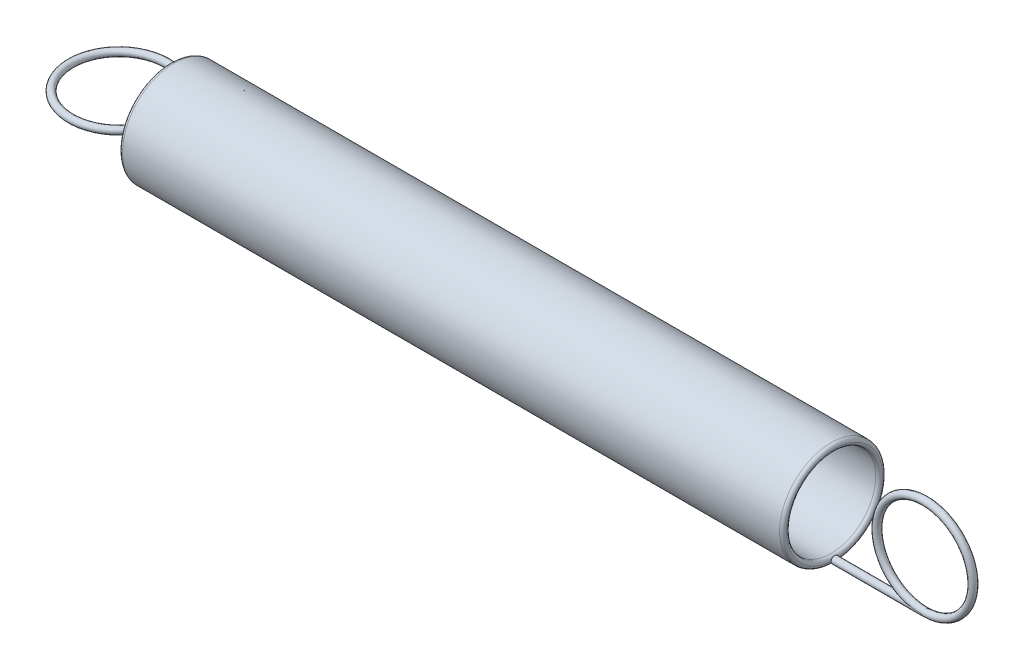
SolidWorks part; units mm, degrees
ref_plane "Front Plane" through (0, 0, 0) normal (0, 0, 1) x (1, 0, 0)
ref_plane "Top Plane" through (0, 0, 0) normal (0, 1, 0) x (1, 0, 0)
ref_plane "Right Plane" through (0, 0, 0) normal (1, 0, 0) x (0, 0, -1)
sketch "Sketch1" plane through (0, 0, 0) normal (0, 1, 0) x (1, 0, 0)
  line L0 (8, 0) -> (59.5, 0) construction
  line L1 (8, 4) -> (59.5, 4)
  line L2 (8, 4) -> (8, -4)
  line L3 (8, -4) -> (59.5, -4)
  line L4 (59.5, 4) -> (59.5, -4)
  line L5 (59.5, 0) -> (70.5, 0)
  line L6 (0, 0) -> (4, 0) construction
  circle A0 centre (4, 0) radius 4
  circle A1 centre (4, 0) radius 3.45
  dimension "D1" = 8
  dimension "D2" = 6.9
  dimension "D3" = 70.5
  dimension "D4" = 11
sketch "Sketch2" plane through (0, 0, 0) normal (0, 0, 1) x (1, 0, 0)
  line L0 (8, 0) -> (0, 0) construction
  line L1 (4, 0) -> (4, 1.1131) construction
  circle A0 centre (0.275, 0) radius 0.275
  dimension "D1" = 0.55
revolve "Revolve1" add sketch "Sketch2" angle 360 about L1
sketch "Sketch3" plane through (0, 0, 0) normal (0, 0, 1) x (1, 0, 0)
  line L0 (8, 0) -> (59.5, 0) construction
  line L1 (8, 0) -> (59.5, 0) construction
  line L2 (8, 0) -> (8, 4) construction
  line L3 (8, 4) -> (59.5, 4)
  line L4 (59.5, 0) -> (59.5, 4) construction
  line L5 (59.5, 0) -> (70.5, 0) construction
  line L6 (8, 4) -> (8, 3.45)
  line L7 (8, 3.45) -> (59.5, 3.45)
  line L8 (59.5, 3.45) -> (59.5, 4)
  line L9 (8, 0) -> (4, 0) construction
  line L10 (7.45, 0) -> (0.55, 0) construction
  arc A0 (7.725, -0.275) -> (7.725, 0.275) centre (7.725, 0) ccw construction
  dimension "D2" = 0.55
revolve "Revolve2" add sketch "Sketch3" angle 360 about L1
fillet "Fillet1" radius 0.275 4 edges at (8, 0, 3.45) (8, 0, 4) (59.5, 0, 3.45) (59.5, 0, 4)
ref_plane "Plane1" through (59.5, 0, 0) normal (1, 0, 0) x (0, 0, -1)
sketch "Sketch4" plane through (59.5, 0, 0) normal (1, 0, 0) x (0, 0, -1)
  line L0 (0, 0) -> (0, -3.725) construction
  circle A0 centre (0, -3.725) radius 0.275
  circle A2 centre (0, 0) radius 3.725 construction
  circle A3 centre (0, 0) radius 3.45 construction
extrude "Boss-Extrude1" add sketch "Sketch4" along normal blind 7 separate body
sketch "Sketch5" plane through (66.5, 0, 0) normal (1, 0, 0) x (0, 0, -1)
  line L0 (0, 0) -> (4, 0) construction
  line L1 (3.45, 0) -> (-3.45, 0) construction
  circle A0 centre (0, 0) radius 4 construction
  circle A1 centre (0, -3.725) radius 0.275
  circle A2 centre (0, -3.725) radius 0.275
  dimension "D1" = 0
revolve "Revolve3" add sketch "Sketch5" angle 360 about L0
ref_axis "Axis1" through (4, 0, 0) along (0, 1, 0)
ref_point "Point1"
